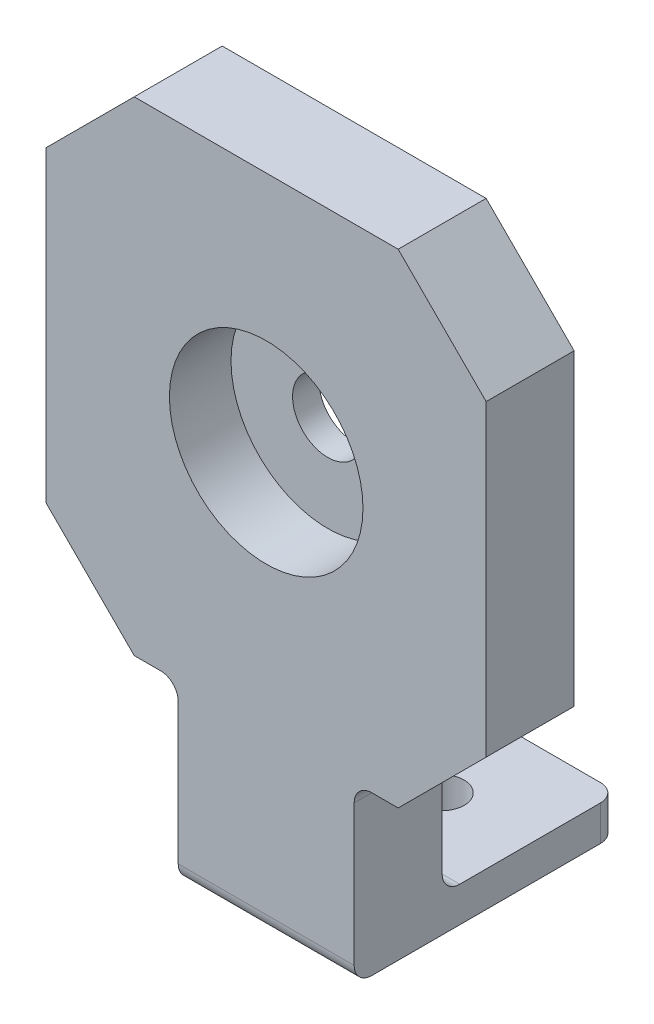
SolidWorks part; units mm, degrees
material "PLA"
ref_plane "Piano frontale" through (0, 0, 0) normal (0, 0, 1) x (1, 0, 0)
ref_plane "Piano superiore" through (0, 0, 0) normal (0, 1, 0) x (1, 0, 0)
ref_plane "Piano destro" through (0, 0, 0) normal (1, 0, 0) x (0, 0, -1)
sketch "Schizzo1" plane through (0, 0, 0) normal (0, 0, 1) x (1, 0, 0)
  line L28 (-25, 20) -> (-10, 20)
  line L37 (-25, 20) -> (-25, 75)
  line L38 (-25, 75) -> (25, 75)
  line L39 (25, 20) -> (25, 75)
  line L40 (-10, 0) -> (10, 0)
  line L41 (-10, 0) -> (-10, 20)
  line L42 (10, 0) -> (10, 20)
  line L43 (10, 20) -> (25, 20)
  circle A5 centre (0, 47.5) radius 4
  point P0 (0, 0)
  point P3 (0, 0)
  point P4 (0, 75)
  dimension "D2" = 15
  dimension "D7" = 27.5
  dimension "D6" = 8
  dimension "D1" = 15
  dimension "D4" = 50
  dimension "D3" = 55
  dimension "D5" = 20
extrude "Estrusione-Estrusione1" add sketch "Schizzo1" along normal blind 10
chamfer "Smusso1" distance 10 angle 45 4 edges at (-25, 75, 5) (-25, 20, 5) (25, 20, 5) (25, 75, 5)
sketch "Schizzo3" plane through (0, 0, 10) normal (0, 0, 1) x (1, 0, 0)
  circle A0 centre (0, 47.5) radius 11
  dimension "D1" = 22
extrude "Taglio-Estrusione1" cut sketch "Schizzo3" against normal blind 7
sketch "Schizzo4" plane through (0, 0, 0) normal (0, 0, -1) x (-1, 0, 0)
  line L0 (10, 20) -> (10, 0) construction
  line L1 (-10, 0) -> (10, 0)
  line L2 (-10, 0) -> (-10, 4)
  line L3 (-10, 4) -> (10, 4)
  line L4 (10, 0) -> (10, 4)
  dimension "D1" = 4
extrude "Estrusione-Estrusione2" add sketch "Schizzo4" along normal blind 20
fillet "Raccordo1" radius 2 6 edges at (0, 0, 10) (0, 4, 0) (-10, 20, 5) (10, 20, 5) (-10, 2, -20) (10, 2, -20)
sketch "Schizzo5" plane through (0, 4, 0) normal (0, 1, 0) x (1, 0, 0)
  line L0 (10, 0) -> (-10, 0) construction
  circle A0 centre (0, 10) radius 2.5
  point P4 (0, 0)
  dimension "D1" = 5
  dimension "D2" = 10
extrude "Taglio-Estrusione2" cut sketch "Schizzo5" against normal blind 20
